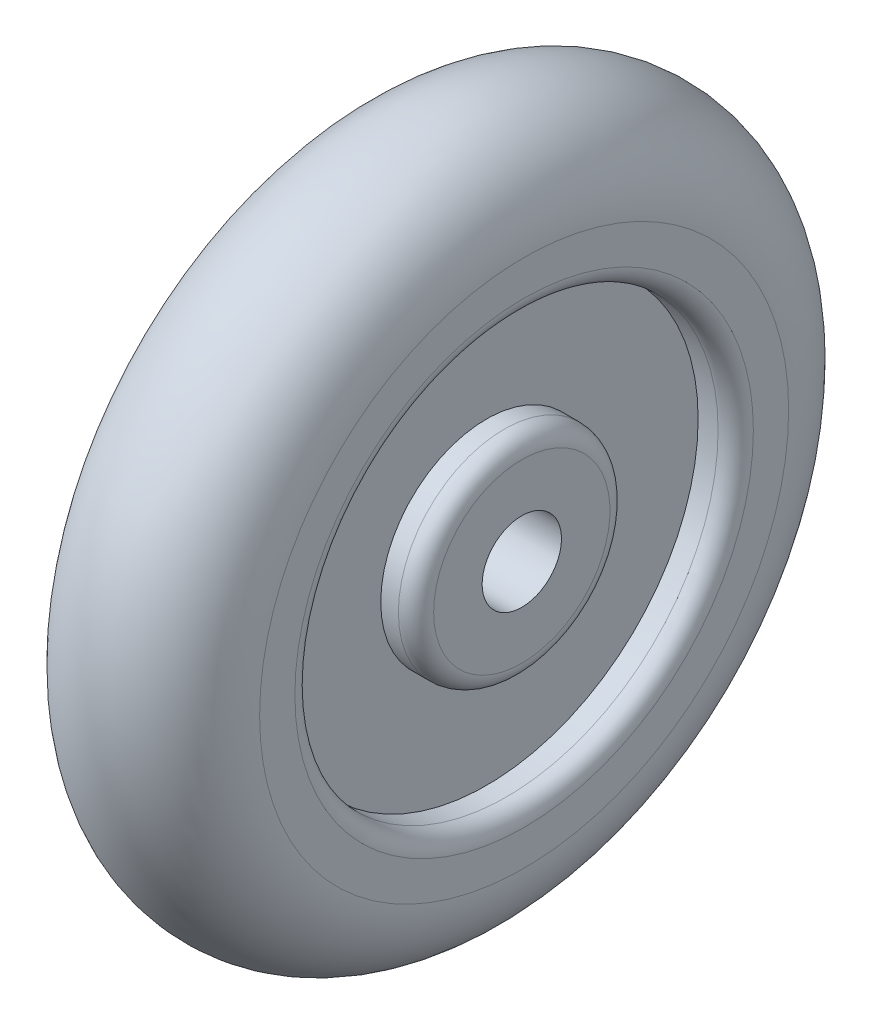
SolidWorks part; units mm, degrees
ref_plane "前基準面" through (0, 0, 0) normal (0, 0, 1) x (1, 0, 0)
ref_plane "上基準面" through (0, 0, 0) normal (0, 1, 0) x (1, 0, 0)
ref_plane "右基準面" through (0, 0, 0) normal (1, 0, 0) x (0, 0, -1)
sketch "草圖1" plane through (0, 0, 0) normal (0, 0, 1) x (1, 0, 0)
  line L0 (-6.6961, 0) -> (7.3695, 0) construction
  line L1 (-2.9338, 0) -> (-2.9338, 6)
  line L2 (-2.9338, 6) -> (-0.9338, 6)
  line L3 (-0.9338, 6) -> (-0.9338, 12)
  line L4 (-0.9338, 12) -> (-2.8026, 12)
  line L5 (-2.8026, 12) -> (-2.8026, 15)
  line L7 (7.1974, 15) -> (7.1974, 12)
  line L8 (7.1974, 12) -> (5.0662, 12)
  line L9 (5.0662, 12) -> (5.0662, 6)
  line L10 (5.0662, 6) -> (7.0662, 6)
  line L11 (7.0662, 6) -> (7.0662, 0)
  line L12 (-2.9338, 0) -> (7.0662, 0)
  arc A1 (7.1974, 15) -> (-2.8026, 15) centre (2.1974, 15) ccw
  dimension "D5" = 5
  dimension "D1" = 6
  dimension "D2" = 2
  dimension "D3" = 12
  dimension "D4" = 2
revolve "旋轉2" add sketch "草圖1" angle 360 about L0
sketch "草圖2" plane through (-2.9338, 0, 0) normal (-1, 0, 0) x (0, 0, 1)
  circle A0 centre (0, 0) radius 2.25
extrude "除料-伸長1" cut sketch "草圖2" against normal through all
fillet "圓角6" radius 1 3 edges at (-0.9338, 0, 12) (-0.9338, 0, 6) (-2.9338, 0, 6)
fillet "圓角7" radius 1 1 edges at (-2.8026, 0, 12)
fillet "圓角9" radius 1 2 edges at (7.0662, 0, 6) (7.1974, 0, 12)
